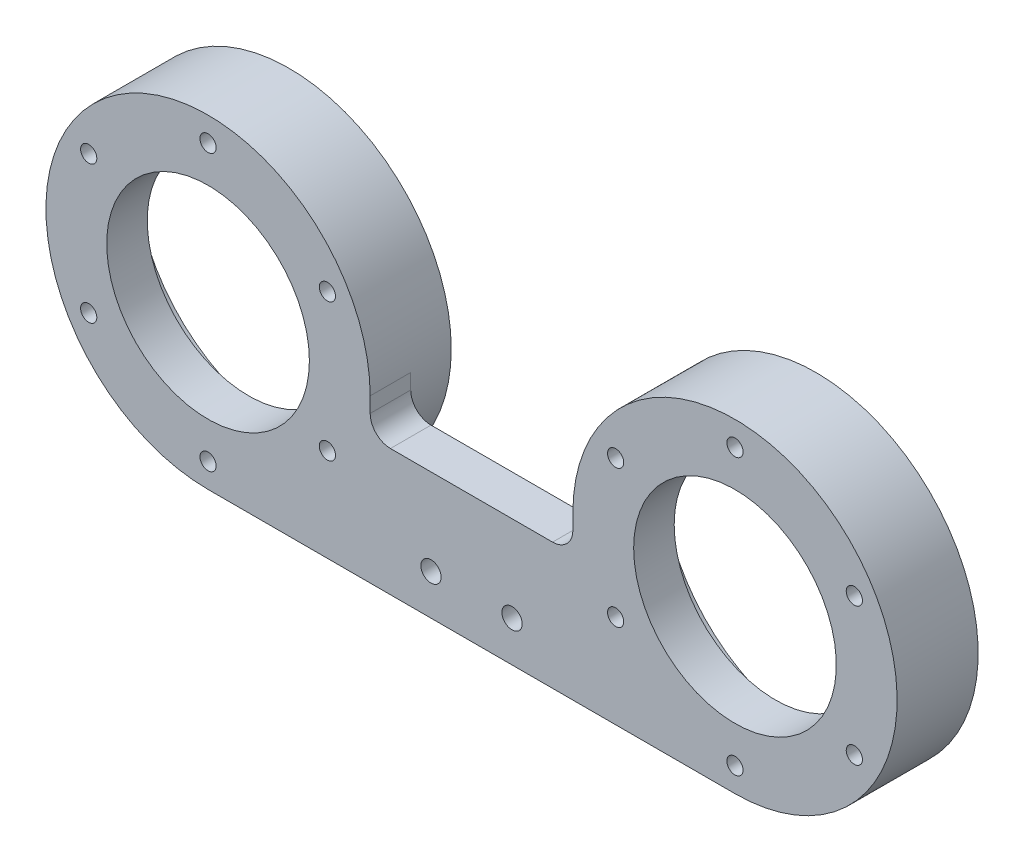
SolidWorks part; units mm, degrees
ref_plane "Front Plane" through (0, 0, 0) normal (0, 0, 1) x (1, 0, 0)
ref_plane "Top Plane" through (0, 0, 0) normal (0, 1, 0) x (1, 0, 0)
ref_plane "Right Plane" through (0, 0, 0) normal (1, 0, 0) x (0, 0, -1)
sketch "Sketch1" plane through (0, 0, 0) normal (0, 0, 1) x (1, 0, 0)
  line L0 (0, 0) -> (0, 41.85) construction
  line L2 (0, 0) -> (65, 0) construction
  line L3 (65, 0) -> (65, 40) construction
  line L4 (130, 0) -> (141.6469, 43.4667) construction
  line L5 (130, 0) -> (130, 45) construction
  line L8 (80, 40) -> (80, -40) construction
  line L12 (50, 40) -> (50, -34.2802) construction
  line L19 (0, 40) -> (130, 40)
  line L20 (130, -40) -> (0, -40)
  arc A20 (25, 0) -> (-25, 0) centre (0, 0) ccw
  arc A21 (-25, 0) -> (25, 0) centre (0, 0) ccw
  arc A58 (0, 40) -> (0, -40) centre (0, 0) ccw
  arc A59 (130, 40) -> (130, -40) centre (130, 0) cw
  arc A60 (155, 0) -> (105, 0) centre (130, 0) cw
  arc A61 (105, 0) -> (155, 0) centre (130, 0) cw
  circle A62 centre (0, 0) radius 34 construction
  circle A63 centre (0, 34) radius 2
  circle A64 centre (29.4449, 17) radius 2
  circle A65 centre (29.4449, -17) radius 2
  circle A66 centre (0, -34) radius 2
  circle A67 centre (-29.4449, -17) radius 2
  circle A68 centre (-29.4449, 17) radius 2
  circle A69 centre (130, -34) radius 2
  circle A70 centre (130, 0) radius 34 construction
  circle A71 centre (159.4449, 17) radius 2
  circle A72 centre (159.4449, -17) radius 2
  circle A73 centre (100.5551, -17) radius 2
  circle A74 centre (100.5551, 17) radius 2
  circle A75 centre (130, 34) radius 2
  circle A76 centre (55, 30) radius 2.5
  circle A77 centre (75, 30) radius 2.5
  circle A78 centre (75, -30) radius 2.5
  circle A79 centre (55, -30) radius 2.5
  point P18 (0, 0)
  point P30 (130, 0)
  point P113 (65, -40)
  point P118 (65, -40)
  point P119 (65, -40)
  point P120 (65, -40)
  dimension "D1" = 25
  dimension "D2" = 80
  dimension "D3" = 4
  dimension "D7" = 80
  dimension "D6" = 10
  dimension "D9" = 5
  dimension "D4" = 6
  dimension "D5" = 65
  dimension "D8" = 10
extrude "Boss-Extrude1" add sketch "Sketch1" along normal mid plane 10
sketch "Sketch2" plane through (0, 0, -5) normal (0, 0, -1) x (-1, 0, 0)
  line L0 (-65, -40) -> (-65, 40) construction
  line L1 (-130, 0) -> (-130, 34) construction
  line L2 (0, 0) -> (29, 0) construction
  line L3 (0, 0) -> (0, 34) construction
  line L4 (-130, 0) -> (-159, 0) construction
  line L5 (-130, 25) -> (-130, -25) construction
  circle A5 centre (-130, 0) radius 34 construction
  circle A8 centre (-130, 34) radius 3
  circle A26 centre (-100.5551, 17) radius 3
  circle A27 centre (-100.5551, -17) radius 3
  circle A28 centre (-130, -34) radius 3
  circle A29 centre (-159.4449, -17) radius 3
  circle A30 centre (-159.4449, 17) radius 3
  circle A31 centre (0, 0) radius 34 construction
  circle A32 centre (29.4449, 17) radius 3
  circle A33 centre (29.4449, -17) radius 3
  circle A34 centre (0, -34) radius 3
  circle A35 centre (-29.4449, -17) radius 3
  circle A36 centre (-29.4449, 17) radius 3
  circle A37 centre (0, 34) radius 3
  circle A38 centre (-130, 0) radius 25 construction
  point P19 (-130, 0)
  point P34 (0, 0)
  point P35 (-130, 0)
  dimension "D1" = 68
  dimension "D2" = 6
extrude "Cut-Extrude2" cut sketch "Sketch2" against normal blind 5
ref_plane "Plane1" through (100, 0, 0) normal (1, 0, 0) x (0, 0, -1)
sketch "Sketch6" plane through (0, 0, -5) normal (0, 0, 1) x (1, 0, 0)
  line L0 (65, 40) -> (65, -40) construction
  circle A0 centre (0, 0) radius 38
  circle A1 centre (0, 0) radius 40
  circle A3 centre (130, 0) radius 40
  circle A4 centre (130, 0) radius 38
  arc A5 (0, 40) -> (0, -40) centre (0, 0) ccw construction
  dimension "D1" = 76
extrude "Boss-Extrude2" add sketch "Sketch6" against normal blind 10
sketch "Sketch7" plane through (0, 0, 5) normal (0, 0, 1) x (1, 0, 0)
  line L0 (40, 0) -> (85.2786, 0) construction
  line L5 (0, 52.8) -> (130, 52.8)
  line L6 (0, 40) -> (0, 52.8)
  line L7 (40, 0) -> (40, -8.75)
  line L8 (40, -8.75) -> (90, -8.75)
  line L10 (130, 0) -> (93.6935, 0) construction
  line L11 (0, 0) -> (130, 0) construction
  line L12 (130, 0) -> (65, 0) construction
  line L13 (65, 0) -> (65, 40) construction
  line L14 (130, 40) -> (0, 40) construction
  line L15 (65, 40) -> (65, 60.8745) construction
  line L16 (65, 0) -> (65, -44.4069) construction
  line L17 (90, 0) -> (44.7214, 0) construction
  line L18 (90, 0) -> (90, -8.75)
  line L19 (130, 40) -> (130, 52.8)
  arc A0 (40, 0) -> (0, 40) centre (0, 0) ccw
  arc A2 (90, 0) -> (130, 40) centre (130, 0) cw
  point P24 (65, -8.75)
  point P25 (65, 52.8)
  dimension "D1" = 17.5
extrude "Cut-Extrude3" cut sketch "Sketch7" against normal blind 29
fillet "Fillet1" radius 5 2 edges at (40, -8.75, 0) (90, -8.75, 0)
equation "\"c\"=6.25"
